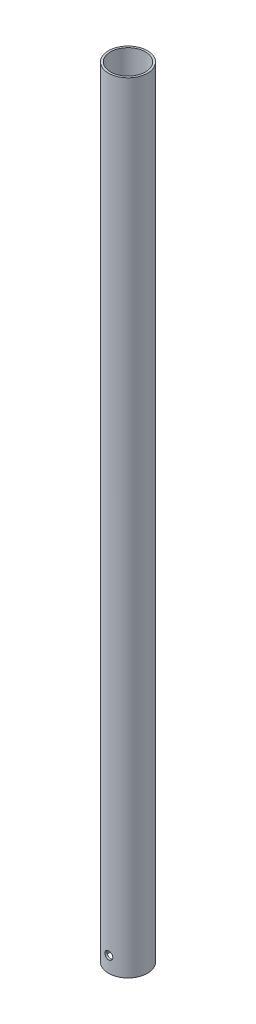
SolidWorks part; units mm, degrees
ref_plane "Front Plane" through (0, 0, 0) normal (0, 0, 1) x (1, 0, 0)
ref_plane "Top Plane" through (0, 0, 0) normal (0, 1, 0) x (1, 0, 0)
ref_plane "Right Plane" through (0, 0, 0) normal (1, 0, 0) x (0, 0, -1)
sketch "Sketch1" plane through (0, 0, 0) normal (0, 1, 0) x (1, 0, 0)
  circle A0 centre (0, 0) radius 15.875
  circle A1 centre (0, 0) radius 14.224
  dimension "D1" = 31.75
  dimension "D2" = 1.651
extrude "Boss-Extrude1" add sketch "Sketch1" along normal blind 635
sketch "Sketch2" plane through (0, 0, 0) normal (0, 0, 1) x (1, 0, 0)
  line L1 (0, 0) -> (0, 570.6762) construction
  line L2 (-15.875, 0) -> (15.875, 0) construction
  circle A0 centre (0, 12.7) radius 3.175
  dimension "D1" = 6.35
  dimension "D3" = 12.7
extrude "Cut-Extrude1" cut sketch "Sketch2" against normal through all both and the other way through all
ref_axis "Axis1" through (0, 639.3507, 0) along (0, -1, 0)
